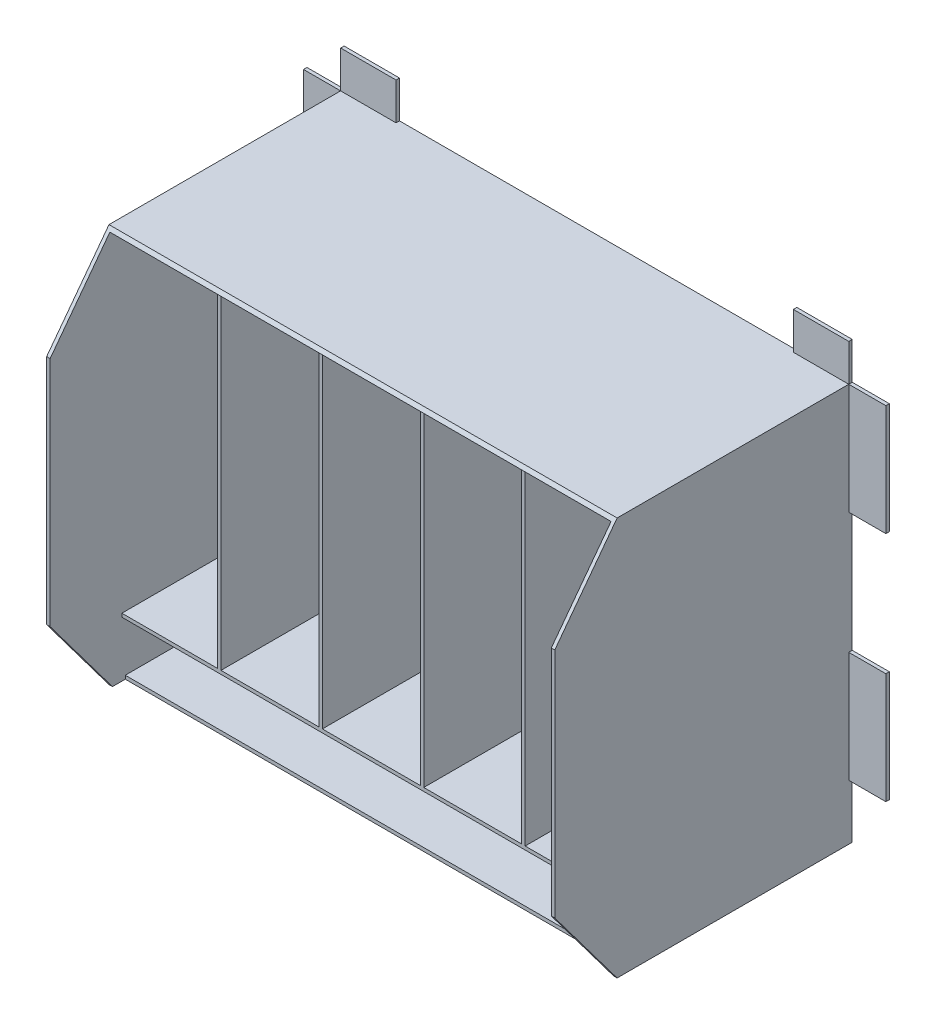
SolidWorks part; units mm, degrees
material "6061-T6 (SS)"
ref_plane "X-Y Datum" through (0, 0, 0) normal (0, 0, 1) x (1, 0, 0)
ref_plane "X-Z Datum" through (0, 0, 0) normal (0, 1, 0) x (1, 0, 0)
ref_plane "Y-Z Datum" through (0, 0, 0) normal (1, 0, 0) x (0, 0, -1)
sketch "Sketch1" plane through (0, 0, 0) normal (0, 0, 1) x (1, 0, 0)
  line L0 (-276.2265, 0) -> (276.2265, 0) construction
  line L1 (-276.2265, 154.041) -> (276.2265, 154.041)
  line L2 (-276.2265, 154.041) -> (-276.2265, -154.041)
  line L3 (-276.2265, -154.041) -> (276.2265, -154.041)
  line L4 (276.2265, 154.041) -> (276.2265, -154.041)
  line L5 (-276.2265, 154.041) -> (276.2265, -154.041) construction
  line L6 (-276.2265, -154.041) -> (276.2265, 154.041) construction
  line L7 (-275.2105, 153.025) -> (-189.6105, 153.025) construction
  line L8 (-275.2105, 153.025) -> (-275.2105, -153.025) construction
  line L9 (-275.2105, -153.025) -> (-189.6105, -153.025) construction
  line L10 (-189.6105, 153.025) -> (-189.6105, -153.025) construction
  line L11 (-275.2105, 153.025) -> (-189.6105, -153.025) construction
  line L12 (-275.2105, -153.025) -> (-189.6105, 153.025) construction
  line L13 (-188.5945, -154.041) -> (-188.5945, 154.041)
  line L14 (-279.4015, 157.216) -> (279.4015, 157.216)
  line L15 (279.4015, 157.216) -> (279.4015, -157.216)
  line L16 (-279.4015, -157.216) -> (279.4015, -157.216)
  line L17 (-279.4015, 157.216) -> (-279.4015, -157.216)
  line L18 (-185.4195, -154.041) -> (-185.4195, 154.041)
  line L19 (-188.5945, 0) -> (-185.4195, 0) construction
  line L20 (-182.2465, 153.025) -> (-182.2465, -153.025) construction
  line L21 (-182.2465, 153.025) -> (-96.6465, 153.025) construction
  line L22 (-96.6465, 153.025) -> (-96.6465, -153.025) construction
  line L23 (-182.2465, -153.025) -> (-96.6465, -153.025) construction
  line L24 (-95.6305, -154.041) -> (-95.6305, 154.041)
  line L25 (-92.4555, -154.041) -> (-92.4555, 154.041)
  line L26 (-89.2825, 153.025) -> (-89.2825, -153.025) construction
  line L27 (-89.2825, 153.025) -> (-3.6825, 153.025) construction
  line L28 (-3.6825, 153.025) -> (-3.6825, -153.025) construction
  line L29 (-89.2825, -153.025) -> (-3.6825, -153.025) construction
  line L30 (-2.6665, -154.041) -> (-2.6665, 154.041)
  line L31 (0.5085, -154.041) -> (0.5085, 154.041)
  line L32 (3.6815, 153.025) -> (3.6815, -153.025) construction
  line L33 (3.6815, 153.025) -> (89.2815, 153.025) construction
  line L34 (89.2815, 153.025) -> (89.2815, -153.025) construction
  line L35 (3.6815, -153.025) -> (89.2815, -153.025) construction
  line L36 (90.2975, -154.041) -> (90.2975, 154.041)
  line L37 (93.4725, -154.041) -> (93.4725, 154.041)
  line L38 (96.6455, 153.025) -> (96.6455, -153.025) construction
  line L39 (96.6455, 153.025) -> (182.2455, 153.025) construction
  line L40 (182.2455, 153.025) -> (182.2455, -153.025) construction
  line L41 (96.6455, -153.025) -> (182.2455, -153.025) construction
  line L42 (183.2615, -154.041) -> (183.2615, 154.041)
  line L43 (186.4365, -154.041) -> (186.4365, 154.041)
  line L44 (-182.2465, -153.025) -> (-96.6465, 153.025) construction
  line L45 (-182.2465, 153.025) -> (-96.6465, -153.025) construction
  line L46 (-89.2825, -153.025) -> (-3.6825, 153.025) construction
  line L47 (-89.2825, 153.025) -> (-3.6825, -153.025) construction
  line L48 (3.6815, -153.025) -> (89.2815, 153.025) construction
  line L49 (3.6815, 153.025) -> (89.2815, -153.025) construction
  line L50 (96.6455, -153.025) -> (182.2455, 153.025) construction
  line L51 (96.6455, 153.025) -> (182.2455, -153.025) construction
  line L52 (-276.2265, -157.216) -> (-276.2265, -204.841)
  line L53 (-279.4015, -157.216) -> (279.4015, -157.216)
  line L54 (-279.4015, -157.216) -> (-279.4015, -208.016)
  line L55 (-279.4015, -208.016) -> (279.4015, -208.016)
  line L56 (279.4015, -157.216) -> (279.4015, -208.016)
  line L57 (-276.2265, -204.841) -> (276.2265, -204.841)
  line L58 (276.2265, -157.216) -> (276.2265, -204.841)
  line L59 (186.4365, -154.041) -> (186.4365, -208.016)
  line L60 (183.2615, -157.216) -> (183.2615, -204.841)
  line L61 (186.4365, 154.041) -> (186.4365, 157.216)
  point P0 (0, 0)
  point P6 (-232.4105, 0)
  point P23 (-187.007, 0)
  point P24 (-139.4465, 0)
  dimension "D1" = 306.05
  dimension "D2" = 85.6
  dimension "D3" = 1.016
  dimension "D4" = 1.016
  dimension "D5" = 1.016
  dimension "D8" = 45.4035
  dimension "D10" = 89.789
  dimension "D12" = 92.964
  dimension "D13" = 89.79
  dimension "D14" = 50.8
  dimension "D6" = 3.175
  dimension "D7" = 3.175
  dimension "D15" = 3.175
  dimension "D9" = 5
  dimension "D11" = 5
extrude "Boss-Extrude1" add sketch "Sketch1" along normal blind 3.175 contours L60 L16 L52 L57 | L53 L60 L57 L59 | L59 L57 L52 L16 L54 L55 | L1 L61 L14 L17 L16 L53 L59 L3 L2 | L3 L42 L1 L37 | L3 L43 L1 L42 | L3 L36 L1 L31 | L3 L37 L1 L36 | L3 L30 L1 L25 | L3 L24 L1 L18 | L3 L13 L1 L2 | L3 L18 L1 L13 | L3 L25 L1 L24 | L3 L31 L1 L30 region at (-276.7885, 0, 0) region at (-232.4105, 0, 0) region at (-187.007, 0, 0) region at (-140.525, 0, 0) region at (-94.043, 0, 0) region at (-47.561, 0, 0) region at (-1.079, 0, 0) region at (45.403, 0, 0) region at (91.885, 0, 0) region at (138.367, 0, 0) region at (184.849, 0, 0) region at (184.849, -181.0285, 0) region at (-46.4825, -181.0285, 0) region at (181.7505, -206.4285, 0)
sketch "Sketch2" plane through (0, 0, 3.175) normal (0, 0, 1) x (1, 0, 0)
  line L0 (-188.5945, -154.041) -> (-188.5945, 154.041) construction
  line L1 (-95.6305, -154.041) -> (-95.6305, 154.041) construction
  line L2 (-185.4195, -154.041) -> (-185.4195, 154.041) construction
  line L3 (90.2975, -154.041) -> (90.2975, 154.041) construction
  line L4 (276.2265, 154.041) -> (-276.2265, 154.041)
  line L5 (276.2265, -154.041) -> (276.2265, 154.041)
  line L6 (-276.2265, -154.041) -> (276.2265, -154.041)
  line L7 (-276.2265, 154.041) -> (-276.2265, -154.041)
  line L8 (276.2265, 154.041) -> (-276.2265, 154.041)
  line L9 (276.2265, -154.041) -> (276.2265, 154.041)
  line L10 (-276.2265, -154.041) -> (276.2265, -154.041)
  line L11 (-276.2265, 154.041) -> (-276.2265, -154.041)
  line L12 (-279.4015, -157.216) -> (279.4015, -157.216)
  line L13 (-279.4015, -157.216) -> (279.4015, -157.216) construction
  line L14 (279.4015, 157.216) -> (279.4015, -157.216) construction
  line L15 (-279.4015, 157.216) -> (279.4015, 157.216) construction
  line L16 (-279.4015, -157.216) -> (279.4015, -157.216)
  line L20 (0.5085, -154.041) -> (0.5085, 154.041) construction
  line L21 (-2.6665, -154.041) -> (-2.6665, 154.041) construction
  line L22 (-92.4555, -154.041) -> (-92.4555, 154.041) construction
  line L23 (186.4365, -154.041) -> (186.4365, 154.041) construction
  line L24 (183.2615, -154.041) -> (183.2615, 154.041) construction
  line L25 (93.4725, -154.041) -> (93.4725, 154.041) construction
  line L26 (-188.5945, -154.041) -> (-188.5945, 154.041)
  line L27 (-95.6305, -154.041) -> (-95.6305, 154.041)
  line L28 (-185.4195, -154.041) -> (-185.4195, 154.041)
  line L29 (90.2975, -154.041) -> (90.2975, 154.041)
  line L30 (0.5085, -154.041) -> (0.5085, 154.041)
  line L31 (-2.6665, -154.041) -> (-2.6665, 154.041)
  line L32 (-92.4555, -154.041) -> (-92.4555, 154.041)
  line L33 (186.4365, -154.041) -> (186.4365, 154.041)
  line L34 (183.2615, -154.041) -> (183.2615, 154.041)
  line L35 (93.4725, -154.041) -> (93.4725, 154.041)
  line L36 (-279.4015, 157.216) -> (-279.4015, -157.216) construction
  line L37 (-279.4015, -157.216) -> (279.4015, -157.216) construction
  line L38 (-279.4015, -157.216) -> (-279.4015, -208.016) construction
  line L39 (-279.4015, -208.016) -> (279.4015, -208.016) construction
  line L40 (279.4015, -157.216) -> (279.4015, -208.016) construction
  line L41 (-276.2265, -157.216) -> (-276.2265, -204.841) construction
  line L42 (-276.2265, -204.841) -> (276.2265, -204.841) construction
  line L43 (276.2265, -157.216) -> (276.2265, -204.841) construction
  line L44 (-276.2265, 154.041) -> (276.2265, 154.041) construction
  line L45 (276.2265, 154.041) -> (276.2265, -154.041) construction
  line L46 (-276.2265, -154.041) -> (276.2265, -154.041) construction
  line L47 (-276.2265, 154.041) -> (-276.2265, -154.041) construction
  line L48 (-188.5945, -154.041) -> (-188.5945, 154.041)
  line L49 (-95.6305, -154.041) -> (-95.6305, 154.041)
  line L50 (-185.4195, -154.041) -> (-185.4195, 154.041)
  line L51 (-279.4015, -157.216) -> (279.4015, -157.216)
  line L52 (279.4015, 157.216) -> (279.4015, -157.216)
  line L53 (-279.4015, 157.216) -> (279.4015, 157.216)
  line L54 (-279.4015, 157.216) -> (-279.4015, -157.216)
  line L55 (-279.4015, -157.216) -> (279.4015, -157.216)
  line L56 (-279.4015, -157.216) -> (-279.4015, -208.016)
  line L57 (-279.4015, -208.016) -> (279.4015, -208.016)
  line L58 (279.4015, -157.216) -> (279.4015, -208.016)
  line L59 (90.2975, -154.041) -> (90.2975, 154.041)
  line L60 (0.5085, -154.041) -> (0.5085, 154.041)
  line L61 (-2.6665, -154.041) -> (-2.6665, 154.041)
  line L62 (-92.4555, -154.041) -> (-92.4555, 154.041)
  line L63 (186.4365, -154.041) -> (186.4365, 154.041)
  line L64 (183.2615, -154.041) -> (183.2615, 154.041)
  line L65 (93.4725, -154.041) -> (93.4725, 154.041)
  line L66 (-276.2265, -157.216) -> (-276.2265, -204.841)
  line L67 (-276.2265, -204.841) -> (276.2265, -204.841)
  line L68 (276.2265, -157.216) -> (276.2265, -204.841)
  line L69 (-276.2265, 154.041) -> (276.2265, 154.041)
  line L70 (276.2265, 154.041) -> (276.2265, -154.041)
  line L71 (-276.2265, -154.041) -> (276.2265, -154.041)
  line L72 (-276.2265, 154.041) -> (-276.2265, -154.041)
  line L73 (183.2615, -157.216) -> (183.2615, -204.841) construction
  line L74 (186.4365, 154.041) -> (186.4365, 157.216) construction
  line L75 (186.4365, -154.041) -> (186.4365, -208.016) construction
  line L76 (-188.5945, -154.041) -> (-188.5945, 154.041)
  line L77 (-95.6305, -154.041) -> (-95.6305, 154.041)
  line L78 (-185.4195, -154.041) -> (-185.4195, 154.041)
  line L79 (-279.4015, -157.216) -> (279.4015, -157.216)
  line L80 (279.4015, 157.216) -> (279.4015, -157.216)
  line L81 (-279.4015, 157.216) -> (279.4015, 157.216)
  line L82 (-279.4015, 157.216) -> (-279.4015, -157.216)
  line L83 (-279.4015, -157.216) -> (279.4015, -157.216)
  line L84 (-279.4015, -157.216) -> (-279.4015, -208.016)
  line L85 (-279.4015, -208.016) -> (279.4015, -208.016)
  line L86 (279.4015, -157.216) -> (279.4015, -208.016)
  line L87 (90.2975, -154.041) -> (90.2975, 154.041)
  line L88 (0.5085, -154.041) -> (0.5085, 154.041)
  line L89 (-2.6665, -154.041) -> (-2.6665, 154.041)
  line L90 (-92.4555, -154.041) -> (-92.4555, 154.041)
  line L91 (183.2615, -154.041) -> (183.2615, 154.041)
  line L92 (93.4725, -154.041) -> (93.4725, 154.041)
  line L93 (183.2615, -157.216) -> (183.2615, -204.841)
  line L94 (-276.2265, -157.216) -> (-276.2265, -204.841)
  line L95 (-276.2265, -204.841) -> (276.2265, -204.841)
  line L96 (276.2265, -157.216) -> (276.2265, -204.841)
  line L97 (186.4365, 154.041) -> (186.4365, 157.216)
  line L98 (186.4365, -154.041) -> (186.4365, 154.041)
  line L99 (186.4365, -154.041) -> (186.4365, -208.016)
  line L100 (-276.2265, 154.041) -> (276.2265, 154.041)
  line L101 (276.2265, 154.041) -> (276.2265, -154.041)
  line L102 (-276.2265, -154.041) -> (276.2265, -154.041)
  line L103 (-276.2265, 154.041) -> (-276.2265, -154.041)
  line M9 (186.4365, 157.216) -> (-279.4015, 157.216)
  line M10 (-279.4015, 157.216) -> (-279.4015, -208.016)
  line M41 (-279.4015, -208.016) -> (186.4365, -208.016)
  line M86 (186.4365, -208.016) -> (186.4365, 157.216)
  dimension "D1" = 0
  dimension "D2" = 0
extrude "Boss-Extrude2" add sketch "Sketch2" along normal blind 200.6 contours L11 L8 L9 L10 M9 M10 | L10 L28 L8 L26 | L10 L32 L8 L27 | L31 L10 L30 L8 | L10 L35 L8 L29 | L34 L10 L33 L8 | L16 L68 L67 L66 M10 M41 | L83 L93 L67 M86 region at (184.849, 0, 3.175) region at (184.849, 154.603, 3.175) region at (91.885, 0, 3.175) region at (184.849, -181.0285, 3.175) region at (181.7505, -206.4285, 3.175) region at (-1.079, 0, 3.175) region at (-94.043, 0, 3.175) region at (-187.007, 0, 3.175)
sketch "Sketch4" plane through (0, -208.016, 0) normal (0, -1, 0) x (1, 0, 0)
  line L0 (-276.2265, 203.775) -> (-276.2265, 3.175)
  line L1 (-276.2265, 3.175) -> (183.2615, 3.175)
  line L2 (183.2615, 3.175) -> (183.2615, 203.775)
  line L4 (-279.4015, 0) -> (186.4365, 0)
  line L5 (186.4365, 0) -> (186.4365, 203.775)
  line L6 (186.4365, 203.775) -> (-279.4015, 203.775)
  line L7 (-279.4015, 203.775) -> (-279.4015, 0)
  line L8 (-279.4015, 0) -> (186.4365, 0)
  line L11 (-279.4015, 203.775) -> (-279.4015, 0)
  line L15 (186.4365, 203.775) -> (-279.4015, 203.775)
  line L16 (186.4365, 0) -> (186.4365, 203.775) construction
  line L18 (186.4365, 0) -> (186.4365, 203.775)
  dimension "D1" = 0
  dimension "D2" = 3.175
extrude "Cut-Extrude1" [suppressed] cut sketch "Sketch4" against normal blind 3.175
sketch "Sketch5" plane through (0, 0, 203.775) normal (0, 0, 1) x (1, 0, 0)
  line L0 (-188.5945, -154.041) -> (-188.5945, 154.041) construction
  line L1 (-95.6305, -154.041) -> (-95.6305, 154.041) construction
  line L2 (-185.4195, -154.041) -> (-185.4195, 154.041) construction
  line L3 (-279.4015, -157.216) -> (279.4015, -157.216) construction
  line L4 (279.4015, 157.216) -> (279.4015, -157.216) construction
  line L5 (-279.4015, 157.216) -> (279.4015, 157.216) construction
  line L6 (-279.4015, 157.216) -> (-279.4015, -157.216) construction
  line L7 (-279.4015, -157.216) -> (279.4015, -157.216) construction
  line L8 (-279.4015, -157.216) -> (-279.4015, -208.016) construction
  line L9 (-279.4015, -208.016) -> (279.4015, -208.016) construction
  line L10 (279.4015, -157.216) -> (279.4015, -208.016) construction
  line L11 (90.2975, -154.041) -> (90.2975, 154.041) construction
  line L12 (0.5085, -154.041) -> (0.5085, 154.041) construction
  line L13 (-2.6665, -154.041) -> (-2.6665, 154.041) construction
  line L14 (-92.4555, -154.041) -> (-92.4555, 154.041) construction
  line L15 (186.4365, -154.041) -> (186.4365, 154.041) construction
  line L16 (183.2615, -154.041) -> (183.2615, 154.041) construction
  line L17 (93.4725, -154.041) -> (93.4725, 154.041) construction
  line L18 (-276.2265, -157.216) -> (-276.2265, -204.841) construction
  line L19 (-276.2265, -204.841) -> (276.2265, -204.841) construction
  line L20 (276.2265, -157.216) -> (276.2265, -204.841) construction
  line L21 (-276.2265, 154.041) -> (276.2265, 154.041) construction
  line L22 (276.2265, 154.041) -> (276.2265, -154.041) construction
  line L23 (-276.2265, -154.041) -> (276.2265, -154.041) construction
  line L24 (-276.2265, 154.041) -> (-276.2265, -154.041) construction
  line L25 (-188.5945, -154.041) -> (-188.5945, 154.041)
  line L26 (-95.6305, -154.041) -> (-95.6305, 154.041)
  line L27 (-185.4195, -154.041) -> (-185.4195, 154.041)
  line L28 (-279.4015, -157.216) -> (279.4015, -157.216)
  line L29 (279.4015, 157.216) -> (279.4015, -157.216)
  line L30 (-279.4015, 157.216) -> (279.4015, 157.216)
  line L31 (-279.4015, 157.216) -> (-279.4015, -157.216)
  line L32 (-279.4015, -157.216) -> (279.4015, -157.216)
  line L33 (-279.4015, -157.216) -> (-279.4015, -208.016)
  line L34 (-279.4015, -208.016) -> (279.4015, -208.016)
  line L35 (279.4015, -157.216) -> (279.4015, -208.016)
  line L36 (90.2975, -154.041) -> (90.2975, 154.041)
  line L37 (0.5085, -154.041) -> (0.5085, 154.041)
  line L38 (-2.6665, -154.041) -> (-2.6665, 154.041)
  line L39 (-92.4555, -154.041) -> (-92.4555, 154.041)
  line L40 (186.4365, -154.041) -> (186.4365, 154.041)
  line L41 (183.2615, -154.041) -> (183.2615, 154.041)
  line L42 (93.4725, -154.041) -> (93.4725, 154.041)
  line L43 (-276.2265, -157.216) -> (-276.2265, -204.841)
  line L44 (-276.2265, -204.841) -> (276.2265, -204.841)
  line L45 (276.2265, -157.216) -> (276.2265, -204.841)
  line L46 (-276.2265, 154.041) -> (276.2265, 154.041)
  line L47 (276.2265, 154.041) -> (276.2265, -154.041)
  line L48 (-276.2265, -154.041) -> (276.2265, -154.041)
  line L49 (-276.2265, 154.041) -> (-276.2265, -154.041)
  line M1 (93.4725, 154.041) -> (183.2615, 154.041)
  line M2 (183.2615, 154.041) -> (183.2615, -154.041)
  line M3 (183.2615, -154.041) -> (93.4725, -154.041)
  line M4 (93.4725, -154.041) -> (93.4725, 154.041)
  line M5 (0.5085, 154.041) -> (90.2975, 154.041)
  line M6 (90.2975, 154.041) -> (90.2975, -154.041)
  line M7 (90.2975, -154.041) -> (0.5085, -154.041)
  line M8 (0.5085, -154.041) -> (0.5085, 154.041)
  line M9 (-92.4555, 154.041) -> (-2.6665, 154.041)
  line M10 (-2.6665, 154.041) -> (-2.6665, -154.041)
  line M11 (-2.6665, -154.041) -> (-92.4555, -154.041)
  line M12 (-92.4555, -154.041) -> (-92.4555, 154.041)
  line M13 (-185.4195, 154.041) -> (-95.6305, 154.041)
  line M14 (-95.6305, 154.041) -> (-95.6305, -154.041)
  line M15 (-95.6305, -154.041) -> (-185.4195, -154.041)
  line M16 (-185.4195, -154.041) -> (-185.4195, 154.041)
  line M17 (-276.2265, 154.041) -> (-188.5945, 154.041)
  line M18 (-188.5945, 154.041) -> (-188.5945, -154.041)
  line M19 (-188.5945, -154.041) -> (-276.2265, -154.041)
  line M20 (-276.2265, -154.041) -> (-276.2265, 154.041)
  line M21 (-276.2265, -208.016) -> (-276.2265, -157.216)
  line M22 (-276.2265, -157.216) -> (183.2615, -157.216)
  line M25 (186.4365, -208.016) -> (186.4365, 157.216)
  line M29 (-279.4015, 157.216) -> (-279.4015, -208.016)
  line M30 (-279.4015, -208.016) -> (-276.2265, -208.016)
  line M32 (186.4365, 157.216) -> (-279.4015, 157.216)
  line M85 (183.2615, -157.216) -> (183.2615, -208.016)
  line M86 (183.2615, -208.016) -> (186.4365, -208.016)
extrude "Boss-Extrude5" add sketch "Sketch5" along normal blind 38.1 contours L44 M85 M86 M25 | L44 L28 M85 M25 | L48 L46 M2 M25 | L48 L46 L28 M19 M20 M17 M13 M9 M5 M1 M25 M32 M29 M22 M3 M7 M11 M15 | L48 L46 M6 M4 | L48 L46 M10 M8 | L48 L46 M14 M12 | L48 L46 M18 M16 | L28 M29 M30 M21 region at (-187.007, -154.603, 203.775) region at (-187.007, 0, 203.775) region at (-94.043, 0, 203.775) region at (-1.079, 0, 203.775) region at (91.885, 0, 203.775) region at (184.849, 0, 203.775) region at (184.849, -181.0285, 203.775) region at (184.849, -206.4285, 203.775) region at (-277.814, -182.616, 203.775)
sketch "Sketch7" plane through (0, 0, 241.875) normal (0, 0, 1) x (1, 0, 0)
  line L0 (-188.5945, -154.041) -> (-188.5945, 154.041) construction
  line L1 (-95.6305, -154.041) -> (-95.6305, 154.041) construction
  line L2 (-185.4195, -154.041) -> (-185.4195, 154.041) construction
  line L3 (-279.4015, -157.216) -> (279.4015, -157.216) construction
  line L4 (279.4015, 157.216) -> (279.4015, -157.216) construction
  line L5 (-279.4015, 157.216) -> (279.4015, 157.216) construction
  line L6 (-279.4015, 157.216) -> (-279.4015, -157.216) construction
  line L7 (-279.4015, -157.216) -> (279.4015, -157.216) construction
  line L8 (-279.4015, -157.216) -> (-279.4015, -208.016) construction
  line L9 (-279.4015, -208.016) -> (279.4015, -208.016) construction
  line L10 (279.4015, -157.216) -> (279.4015, -208.016) construction
  line L11 (90.2975, -154.041) -> (90.2975, 154.041) construction
  line L12 (0.5085, -154.041) -> (0.5085, 154.041) construction
  line L13 (-2.6665, -154.041) -> (-2.6665, 154.041) construction
  line L14 (-92.4555, -154.041) -> (-92.4555, 154.041) construction
  line L15 (186.4365, -154.041) -> (186.4365, 154.041) construction
  line L16 (183.2615, -154.041) -> (183.2615, 154.041) construction
  line L17 (93.4725, -154.041) -> (93.4725, 154.041) construction
  line L18 (-276.2265, -157.216) -> (-276.2265, -204.841) construction
  line L19 (-276.2265, -204.841) -> (276.2265, -204.841) construction
  line L20 (276.2265, -157.216) -> (276.2265, -204.841) construction
  line L21 (-276.2265, 154.041) -> (276.2265, 154.041) construction
  line L22 (276.2265, 154.041) -> (276.2265, -154.041) construction
  line L23 (-276.2265, -154.041) -> (276.2265, -154.041) construction
  line L24 (-276.2265, 154.041) -> (-276.2265, -154.041) construction
  line L25 (-188.5945, -154.041) -> (-188.5945, 154.041)
  line L26 (-95.6305, -154.041) -> (-95.6305, 154.041)
  line L27 (-185.4195, -154.041) -> (-185.4195, 154.041)
  line L28 (-279.4015, -157.216) -> (279.4015, -157.216)
  line L29 (279.4015, 157.216) -> (279.4015, -157.216)
  line L30 (-279.4015, 157.216) -> (279.4015, 157.216)
  line L31 (-279.4015, 157.216) -> (-279.4015, -157.216)
  line L32 (-279.4015, -157.216) -> (279.4015, -157.216)
  line L33 (-279.4015, -157.216) -> (-279.4015, -208.016)
  line L34 (-279.4015, -208.016) -> (279.4015, -208.016)
  line L35 (279.4015, -157.216) -> (279.4015, -208.016)
  line L36 (90.2975, -154.041) -> (90.2975, 154.041)
  line L37 (0.5085, -154.041) -> (0.5085, 154.041)
  line L38 (-2.6665, -154.041) -> (-2.6665, 154.041)
  line L39 (-92.4555, -154.041) -> (-92.4555, 154.041)
  line L40 (186.4365, -154.041) -> (186.4365, 154.041)
  line L41 (183.2615, -154.041) -> (183.2615, 154.041)
  line L42 (93.4725, -154.041) -> (93.4725, 154.041)
  line L43 (-276.2265, -157.216) -> (-276.2265, -204.841)
  line L44 (-276.2265, -204.841) -> (276.2265, -204.841)
  line L45 (276.2265, -157.216) -> (276.2265, -204.841)
  line L46 (-276.2265, 154.041) -> (276.2265, 154.041)
  line L47 (276.2265, 154.041) -> (276.2265, -154.041)
  line L48 (-276.2265, -154.041) -> (276.2265, -154.041)
  line L49 (-276.2265, 154.041) -> (-276.2265, -154.041)
  line L50 (-276.2265, -154.041) -> (-276.2265, -157.216)
  line L51 (276.2265, -154.041) -> (276.2265, -157.216)
  line L52 (183.2615, -154.041) -> (186.4365, -154.041)
  line L53 (183.2615, 154.041) -> (186.4365, 154.041)
  line L54 (183.2615, -154.041) -> (183.2615, -157.216)
  line M1 (-95.6305, -154.041) -> (-185.4195, -154.041)
  line M2 (-185.4195, -154.041) -> (-185.4195, 154.041)
  line M4 (-95.6305, 154.041) -> (-95.6305, -154.041)
  line M5 (-2.6665, -154.041) -> (-92.4555, -154.041)
  line M6 (-92.4555, -154.041) -> (-92.4555, 154.041)
  line M8 (-2.6665, 154.041) -> (-2.6665, -154.041)
  line M9 (90.2975, -154.041) -> (0.5085, -154.041)
  line M10 (0.5085, -154.041) -> (0.5085, 154.041)
  line M12 (90.2975, 154.041) -> (90.2975, -154.041)
  line M13 (183.2615, -154.041) -> (93.4725, -154.041)
  line M14 (93.4725, -154.041) -> (93.4725, 154.041)
  line M21 (-188.5945, -154.041) -> (-276.2265, -154.041)
  line M24 (-188.5945, 154.041) -> (-188.5945, -154.041)
  line M28 (-276.2265, -157.216) -> (183.2615, -157.216)
extrude "Cut-Extrude2" cut sketch "Sketch7" against normal blind 35 contours L54 L48 L50 M13 M9 M5 M1 M21 M28 | L48 L46 M12 M14 | L48 L46 M4 M6 | L48 L46 M8 M10 | L48 L46 M24 M2 region at (-46.4825, -155.6285, 241.875) region at (-187.007, 0, 241.875) region at (-94.043, 0, 241.875) region at (-1.079, 0, 241.875) region at (91.885, 0, 241.875)
sketch "Sketch8" plane through (0, 0, 241.875) normal (0, 0, 1) x (1, 0, 0)
  line L8 (183.2615, 154.041) -> (183.2615, -208.016)
  line L9 (183.2615, -208.016) -> (186.4365, -208.016)
  line L10 (186.4365, -208.016) -> (186.4365, 157.216)
  line L11 (186.4365, 157.216) -> (-279.4015, 157.216)
  line L12 (-279.4015, 157.216) -> (-279.4015, -208.016)
  line L13 (-279.4015, -208.016) -> (-276.2265, -208.016)
  line L14 (-276.2265, -208.016) -> (-276.2265, 154.041)
  line L16 (183.2615, 154.041) -> (183.2615, -208.016)
  line L17 (183.2615, -208.016) -> (186.4365, -208.016)
  line L18 (186.4365, -208.016) -> (186.4365, 157.216)
  line L19 (186.4365, 157.216) -> (-279.4015, 157.216)
  line L20 (-279.4015, 157.216) -> (-279.4015, -208.016)
  line L21 (-279.4015, -208.016) -> (-276.2265, -208.016)
  line L24 (-276.2265, -208.016) -> (-276.2265, 154.041)
  line L26 (-276.2265, 154.041) -> (183.2615, 154.041)
  line L27 (-276.2265, 154.041) -> (183.2615, 154.041)
  dimension "D1" = 0
extrude "Boss-Extrude6" add sketch "Sketch8" along normal blind 30.8
sketch "Sketch9" plane through (186.4365, 0, 0) normal (1, 0, 0) x (0, 0, -1)
  line L0 (-215.525, -208.016) -> (-272.675, -131.816)
  line L1 (-272.675, -208.016) -> (0, -208.016) construction
  line L2 (-215.525, 157.216) -> (-272.675, 81.016)
  line L4 (0, -208.016) -> (0, 157.216)
  line L5 (0, 157.216) -> (-272.675, 157.216)
  line L6 (-272.675, 157.216) -> (-272.675, -208.016)
  line L7 (-272.675, -208.016) -> (0, -208.016)
  line L8 (0, -208.016) -> (0, 157.216)
  line L9 (0, 157.216) -> (-272.675, 157.216)
  line L10 (-272.675, 157.216) -> (-272.675, -208.016)
  line L11 (-272.675, -208.016) -> (0, -208.016)
  line M6 (0, 157.216) -> (-272.675, 157.216)
  line M7 (-272.675, 157.216) -> (-272.675, -208.016)
  line M8 (-272.675, -208.016) -> (0, -208.016)
  dimension "D2" = 57.15
  dimension "D3" = 76.2
  dimension "D4" = 76.2
  dimension "D5" = 57.15
  dimension "D1" = 0
extrude "Cut-Extrude3" cut sketch "Sketch9" against normal through all contours L0 M8 M7 | L2 M6 M7 region at (186.4365, -182.616, 253.625) region at (186.4365, 131.816, 253.625)
sketch "Sketch10" plane through (0, 0, 0) normal (0, 0, 1) x (1, 0, 0)
  line L0 (-276.2265, -157.216) -> (183.2615, -157.216) construction
  line L1 (186.4365, 157.216) -> (220.4725, 157.216)
  line L2 (186.4365, 157.216) -> (186.4365, 55.616)
  line L3 (186.4365, 55.616) -> (220.4725, 55.616)
  line L4 (186.4365, -208.016) -> (186.4365, 157.216)
  line L5 (-279.4015, -208.016) -> (186.4365, -208.016)
  line L6 (-279.4015, 157.216) -> (-279.4015, -208.016)
  line L7 (186.4365, 157.216) -> (-279.4015, 157.216)
  line L8 (186.4365, -208.016) -> (186.4365, 157.216)
  line L9 (-279.4015, -208.016) -> (186.4365, -208.016)
  line L10 (-279.4015, 157.216) -> (-279.4015, -208.016)
  line L11 (186.4365, 157.216) -> (-279.4015, 157.216)
  line L12 (220.4725, 157.216) -> (220.4725, 55.616)
  line L13 (-276.2265, -157.216) -> (183.2615, -157.216)
  line L15 (186.4365, -157.216) -> (220.4725, -157.216)
  line L16 (186.4365, -157.216) -> (186.4365, -55.616)
  line L17 (186.4365, -55.616) -> (220.4725, -55.616)
  line L18 (220.4725, -157.216) -> (220.4725, -55.616)
  line L19 (186.4365, 157.216) -> (135.6365, 157.216)
  line L20 (186.4365, 157.216) -> (186.4365, 191.252)
  line L21 (186.4365, 191.252) -> (135.6365, 191.252)
  line L22 (135.6365, 157.216) -> (135.6365, 191.252)
  dimension "D2" = 34.036
  dimension "D3" = 101.6
  dimension "D4" = 50.8
  dimension "D1" = 0
extrude "Boss-Extrude7" add sketch "Sketch10" along normal blind 3.175 contours L12 L1 L2 L3 | L15 L18 L17 L8 | L22 L11 L20 L21 region at (203.4545, 106.416, 0) region at (161.0365, 174.234, 0) region at (203.4545, -106.416, 0)
ref_plane "Plane1" through (-46.4825, 0, 0) normal (-1, 0, 0) x (0, 0, 1)
mirror "Mirror1" about plane through (-46.4825, 0, 0) normal (-1, 0, 0) of "Boss-Extrude7"
